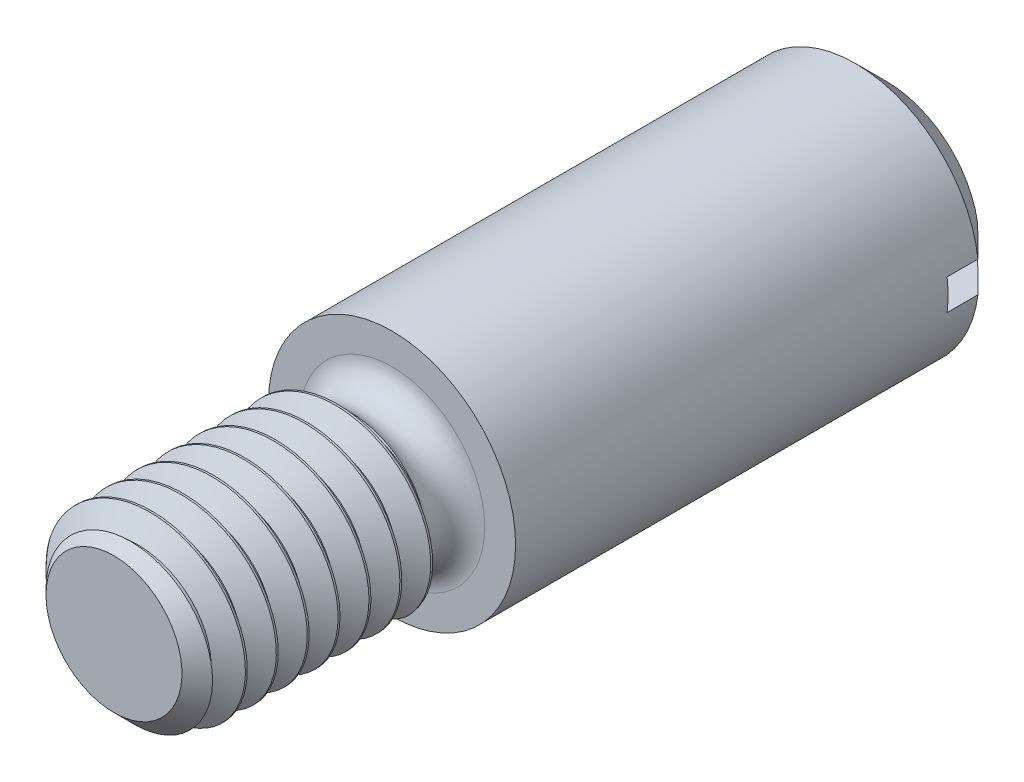
SolidWorks part; units mm, degrees
material "Cast Alloy Steel"
ref_plane "Front Plane" through (0, 0, 0) normal (0, 0, 1) x (1, 0, 0)
ref_plane "Top Plane" through (0, 0, 0) normal (0, 1, 0) x (1, 0, 0)
ref_plane "Right Plane" through (0, 0, 0) normal (1, 0, 0) x (0, 0, -1)
sketch "Sketch1" plane through (0, 0, 0) normal (1, 0, 0) x (0, 0, -1)
  line L0 (6.25, 0) -> (-6.25, 0) construction
  line L1 (-6.25, 0) -> (-6.25, 1.1)
  line L2 (-6.25, 1.1) -> (-5.85, 1.5)
  line L3 (-5.85, 1.5) -> (-2.5619, 1.5)
  line L4 (-1.75, 1.5) -> (-1.75, 2)
  line L5 (-1.75, 2) -> (5.75, 2)
  line L6 (5.75, 2) -> (6.25, 1.5)
  line L7 (6.25, 1.5) -> (6.25, 0)
  line L12 (-6.4844, 1.5) -> (-6.25, 1.5) construction
  line L14 (-6.25, 1.5) -> (-6.25, -1.5) construction
  line L15 (6.25, 0.25) -> (5.25, 0.25) construction
  line L16 (5.25, 0.25) -> (5.25, -0.25) construction
  line L17 (5.25, -0.25) -> (6.25, -0.25) construction
  line L18 (6.25, 0) -> (-6.25, 0)
  line L21 (-6.7344, 1.5271) -> (-6.2344, 1.5271) construction
  line L22 (-6.2344, 1.5271) -> (-6.4844, 1.0941) construction
  line L23 (-6.4844, 1.0941) -> (-6.7344, 1.5271) construction
  line L24 (-6.4844, 1.5271) -> (-6.4844, 1.4729) construction
  line L25 (-6.4844, 1.1482) -> (-6.4844, 1.0941) construction
  line L26 (-6.7031, 1.4729) -> (-6.2656, 1.4729) construction
  line L27 (-6.5156, 1.1482) -> (-6.4531, 1.1482) construction
  arc A0 (-2.5619, 1.5) -> (-1.75, 1.5) centre (-2.1559, 1.5) ccw
  point P22 (-5, -1.5)
  point P27 (5.25, 0)
  point P29 (-2.1559, 1.0941)
  dimension "D3" = 0.4
  dimension "D4" = 45
  dimension "Thread Size" = 3
  dimension "Shoulder Length" = 8
  dimension "Shoulder Dia" = 4
  dimension "Thread Length" = 4.5
  dimension "D6" = 1.25
  dimension "T" = 1
  dimension "N" = 0.5
  dimension "Z1" = 0.5
  dimension "D7" = 45
  dimension "D8" = 0.0625
  dimension "Pitch" = 0.5
revolve "Revolve1" add sketch "Sketch1" angle 360 about L18
sketch "Sketch2" plane through (0, 0, -6.25) normal (0, 0, -1) x (-1, 0, 0)
  line L1 (-2, 0.25) -> (2, 0.25)
  line L2 (-2, 0.25) -> (-2, -0.25)
  line L3 (-2, -0.25) -> (2, -0.25)
  line L4 (2, 0.25) -> (2, -0.25)
  circle A0 centre (0, 0) radius 2 construction
  circle A1 centre (0, 0) radius 2 construction
extrude "Cut-Extrude1" cut sketch "Sketch2" against normal up to vertex (1 mm away) up to point (0, 0.25, -5.25)
sketch "Sketch3" plane through (0, 0, 6.25) normal (0, 0, 1) x (1, 0, 0)
  circle A0 centre (0, 0) radius 1.5
curve "Helix/Spiral1" pitch 0.5 height 4.25 radius 1.5 centre (0, 0, 6.25) axis (0, 0, -1) start towards (0, 1, 0)
sketch "Sketch4" plane through (0, 0, 0) normal (1, 0, 0) x (0, 0, -1)
  line L8 (-6.5156, 1.1482) -> (-6.4531, 1.1482)
  line L9 (-6.4531, 1.1482) -> (-6.25, 1.5)
  line L10 (-6.25, 1.5) -> (-6.7187, 1.5)
  line L11 (-6.4844, 1.0941) -> (-6.7344, 1.5271) construction
  line L12 (-6.7187, 1.5) -> (-6.5156, 1.1482)
sweep "Cut-Sweep3" cut profiles "Sketch4" path "Helix/Spiral1"
ref_axis "Center Axis 1" through (0, 0, 6.6) along (0, 0, -1)
ref_plane "Contact Plane 1" through (0, 0, 1.75) normal (0, 0, 1) x (1, 0, 0)
equation "\"D3@Sketch1\"=\"Pitch@Sketch1\"*.8"
equation "\"D6@Sketch1\"=\"Pitch@Sketch1\"*2.50"
equation "\"D3@Helix/Spiral1\"=\"Thread Length@Sketch1\"-(\"Pitch@Sketch1\"*.5)"
equation "\"D4@Helix/Spiral1\"=\"Pitch@Sketch1\""
equation "\"D8@Sketch1\"=\"Pitch@Sketch1\"/8"
